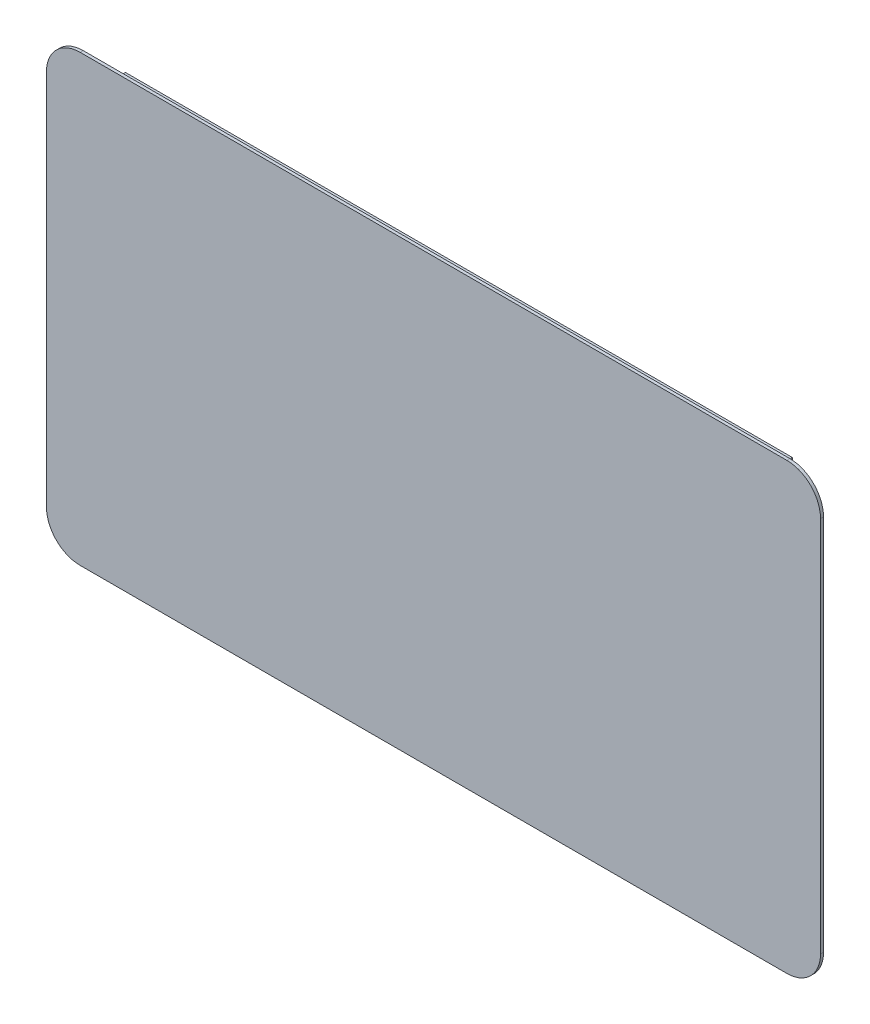
SolidWorks part; units mm, degrees
ref_plane "前视基准面" through (0, 0, 0) normal (0, 0, 1) x (1, 0, 0)
ref_plane "上视基准面" through (0, 0, 0) normal (0, 1, 0) x (1, 0, 0)
ref_plane "右视基准面" through (0, 0, 0) normal (1, 0, 0) x (0, 0, -1)
sketch "草图1" plane through (0, 0, 0) normal (0, 0, 1) x (1, 0, 0)
  line L1 (-96.5, 55.4) -> (96.5, 55.4)
  line L2 (-96.5, 55.4) -> (-96.5, -55.4)
  line L3 (-96.5, -55.4) -> (96.5, -55.4)
  line L4 (96.5, 55.4) -> (96.5, -55.4)
  line L5 (-96.5, 55.4) -> (96.5, -55.4) construction
  line L6 (-96.5, -55.4) -> (96.5, 55.4) construction
  point P0 (0, 0)
  dimension "D1" = 193
  dimension "D2" = 110.8
extrude "凸台-拉伸1" add sketch "草图1" along normal blind 0.75
fillet "圆角1" radius 8.4 4 edges at (96.5, 55.4, 0.375) (-96.5, -55.4, 0.375) (-96.5, 55.4, 0.375) (96.5, -55.4, 0.375)
sketch "草图2" plane through (0, 0, 0) normal (0, 0, -1) x (-1, 0, 0)
  line L0 (-88.1, 55.4) -> (88.1, 55.4) construction
  line L1 (-83.15, 50.35) -> (83.15, 50.35)
  line L2 (-83.15, 50.35) -> (-83.15, -50.35)
  line L3 (-83.15, -50.35) -> (83.15, -50.35)
  line L4 (83.15, 50.35) -> (83.15, -50.35)
  line L5 (-83.15, 50.35) -> (83.15, -50.35) construction
  line L6 (-83.15, -50.35) -> (83.15, 50.35) construction
  line L7 (96.5, 47) -> (96.5, -47) construction
  point P0 (0, 0)
  point P9 (0, 55.4)
  point P13 (96.5, 0)
  dimension "D1" = 166.3
  dimension "D2" = 100.7
extrude "凸台-拉伸2" add sketch "草图2" along normal blind 5.6
sketch "草图3" plane through (0, 0, -5.6) normal (0, 0, -1) x (-1, 0, 0)
  line L0 (63.961, 34.1) -> (116.6112, 34.1) construction
  line L1 (-63, 66.4634) -> (-63, 21.8208) construction
  line L2 (-116.6112, -31.9) -> (-26.1249, -31.9) construction
  line L3 (63, 63.6607) -> (63, 9.2088) construction
  line L4 (-88.1, 55.4) -> (88.1, 55.4) construction
  line L5 (88.1, -55.4) -> (-88.1, -55.4) construction
  line L6 (-96.5, -47) -> (-96.5, 47) construction
  line L7 (96.5, 47) -> (96.5, -47) construction
  line L9 (-66, 38.1) -> (-60, 38.1)
  line L10 (-66, 38.1) -> (-66, 30.1)
  line L11 (-66, 30.1) -> (-60, 30.1)
  line L12 (-60, 38.1) -> (-60, 30.1)
  line L13 (-66, 38.1) -> (-60, 30.1) construction
  line L14 (-66, 30.1) -> (-60, 38.1) construction
  line L15 (-66, -27.9) -> (-60, -27.9)
  line L16 (-66, -27.9) -> (-66, -35.9)
  line L17 (-66, -35.9) -> (-60, -35.9)
  line L18 (-60, -27.9) -> (-60, -35.9)
  line L19 (-66, -27.9) -> (-60, -35.9) construction
  line L20 (-66, -35.9) -> (-60, -27.9) construction
  line L21 (60, 38.1) -> (66, 38.1)
  line L22 (60, 38.1) -> (60, 30.1)
  line L23 (60, 30.1) -> (66, 30.1)
  line L24 (66, 38.1) -> (66, 30.1)
  line L25 (60, 38.1) -> (66, 30.1) construction
  line L26 (60, 30.1) -> (66, 38.1) construction
  line L27 (60, -27.9) -> (66, -27.9)
  line L28 (60, -27.9) -> (60, -35.9)
  line L29 (60, -35.9) -> (66, -35.9)
  line L30 (66, -27.9) -> (66, -35.9)
  line L31 (60, -27.9) -> (66, -35.9) construction
  line L32 (60, -35.9) -> (66, -27.9) construction
  point P16 (-63, 34.1)
  point P21 (-63, -31.9)
  point P26 (63, 34.1)
  point P31 (63, -31.9)
  dimension "D1" = 21.3
  dimension "D2" = 23.5
  dimension "D3" = 33.5
  dimension "D4" = 33.5
  dimension "D5" = 8
  dimension "D6" = 6
extrude "凸台-拉伸3" add sketch "草图3" along normal blind 2.34
chamfer "倒角1" distance 2.34 angle 45 8 edges at (66, -31.9, -5.6) (60, -31.9, -5.6) (-66, -31.9, -5.6) (-60, -31.9, -5.6) (-60, 34.1, -5.6) (-66, 34.1, -5.6) (60, 34.1, -5.6) (66, 34.1, -5.6)
sketch "草图4" plane through (0, 0, -7.94) normal (0, 0, -1) x (-1, 0, 0)
  line L0 (-60, 38.1) -> (-66, 38.1) construction
  line L1 (66, 38.1) -> (60, 38.1) construction
  line L2 (66, -35.9) -> (66, -27.9) construction
  line L3 (66, 30.1) -> (66, 38.1) construction
  circle A0 centre (-63, 34.1) radius 1.35
  circle A1 centre (-63, -31.9) radius 1.35
  circle A2 centre (63, -31.9) radius 1.35
  circle A3 centre (63, 34.1) radius 1.35
  point P11 (-63, 38.1)
  point P14 (63, 38.1)
  point P17 (66, -31.9)
  point P20 (66, 34.1)
  dimension "D1" = 2.7
extrude "切除-拉伸1" cut sketch "草图4" against normal blind 2.34
sketch "草图5" plane through (0, 0, -5.6) normal (0, 0, -1) x (-1, 0, 0)
  line L0 (-108.4034, 31.4) -> (-36.735, 31.4) construction
  line L1 (-96.5, -47) -> (-96.5, 47) construction
  line L2 (-108.4034, -17.6) -> (-38.5367, -17.6) construction
  line L3 (96.5, 47) -> (96.5, -47) construction
  line L4 (22.2, -23.2221) -> (22.2, 22.8218) construction
  line L5 (-88.1, 55.4) -> (88.1, 55.4) construction
  line L6 (-35.8, 22.8218) -> (-35.8, -24.6235) construction
  line L7 (88.1, -55.4) -> (-88.1, -55.4) construction
  line L9 (-39.7, 35.3) -> (-31.9, 35.3)
  line L10 (-39.7, 35.3) -> (-39.7, 27.5)
  line L11 (-39.7, 27.5) -> (-31.9, 27.5)
  line L12 (-31.9, 35.3) -> (-31.9, 27.5)
  line L13 (-39.7, 35.3) -> (-31.9, 27.5) construction
  line L14 (-39.7, 27.5) -> (-31.9, 35.3) construction
  line L15 (18.3, 35.3) -> (26.1, 35.3)
  line L16 (18.3, 35.3) -> (18.3, 27.5)
  line L17 (18.3, 27.5) -> (26.1, 27.5)
  line L18 (26.1, 35.3) -> (26.1, 27.5)
  line L19 (18.3, 35.3) -> (26.1, 27.5) construction
  line L20 (18.3, 27.5) -> (26.1, 35.3) construction
  line L21 (-39.7, -13.7) -> (-31.9, -13.7)
  line L22 (-39.7, -13.7) -> (-39.7, -21.5)
  line L23 (-39.7, -21.5) -> (-31.9, -21.5)
  line L24 (-31.9, -13.7) -> (-31.9, -21.5)
  line L25 (-39.7, -13.7) -> (-31.9, -21.5) construction
  line L26 (-39.7, -21.5) -> (-31.9, -13.7) construction
  line L27 (18.3, -13.7) -> (26.1, -13.7)
  line L28 (18.3, -13.7) -> (18.3, -21.5)
  line L29 (18.3, -21.5) -> (26.1, -21.5)
  line L30 (26.1, -13.7) -> (26.1, -21.5)
  line L31 (18.3, -13.7) -> (26.1, -21.5) construction
  line L32 (18.3, -21.5) -> (26.1, -13.7) construction
  point P16 (-35.8, 31.4)
  point P21 (22.2, 31.4)
  point P26 (-35.8, -17.6)
  point P31 (22.2, -17.6)
  dimension "D1" = 60.7
  dimension "D2" = 74.3
  dimension "D3" = 24
  dimension "D4" = 37.8
  dimension "D5" = 7.8
extrude "凸台-拉伸4" add sketch "草图5" along normal blind 2.34
sketch "草图6" plane through (0, 0, -7.94) normal (0, 0, -1) x (-1, 0, 0)
  line L0 (-39.7, 35.3) -> (-39.7, 27.5) construction
  line L1 (-39.4, 35) -> (25.6, 35)
  line L2 (-39.4, 35) -> (-39.4, -21)
  line L3 (-39.4, -21) -> (25.6, -21)
  line L4 (25.6, 35) -> (25.6, -21)
  line L5 (-39.4, 35) -> (25.6, -21) construction
  line L6 (-39.4, -21) -> (25.6, 35) construction
  line L7 (-31.9, 35.3) -> (-39.7, 35.3) construction
  point P0 (-6.9, 7)
  dimension "D1" = 65
  dimension "D2" = 56
  dimension "D3" = 0.3
  dimension "D4" = 0.3
extrude "凸台-拉伸5" add sketch "草图6" along normal blind 1.2
fillet "圆角2" radius 2.5 4 edges at (39.4, -21, -8.54) (-25.6, -21, -8.54) (-25.6, 35, -8.54) (39.4, 35, -8.54)
sketch "草图7" plane through (0, 0, -9.14) normal (0, 0, -1) x (-1, 0, 0)
  line L0 (-88.1, 55.4) -> (88.1, 55.4) construction
  line L1 (88.1, -55.4) -> (-88.1, -55.4) construction
  line L2 (-96.5, -47) -> (-96.5, 47) construction
  line L3 (96.5, 47) -> (96.5, -47) construction
  circle A0 centre (-35.8, 31.4) radius 1.25
  circle A1 centre (22.2, 31.4) radius 1.25
  circle A2 centre (-35.8, -17.6) radius 1.25
  circle A3 centre (22.2, -17.6) radius 1.25
  dimension "D1" = 2.5
  dimension "D2" = 24
  dimension "D3" = 37.8
  dimension "D4" = 60.7
  dimension "D5" = 74.3
extrude "切除-拉伸2" cut sketch "草图7" against normal blind 0.6
